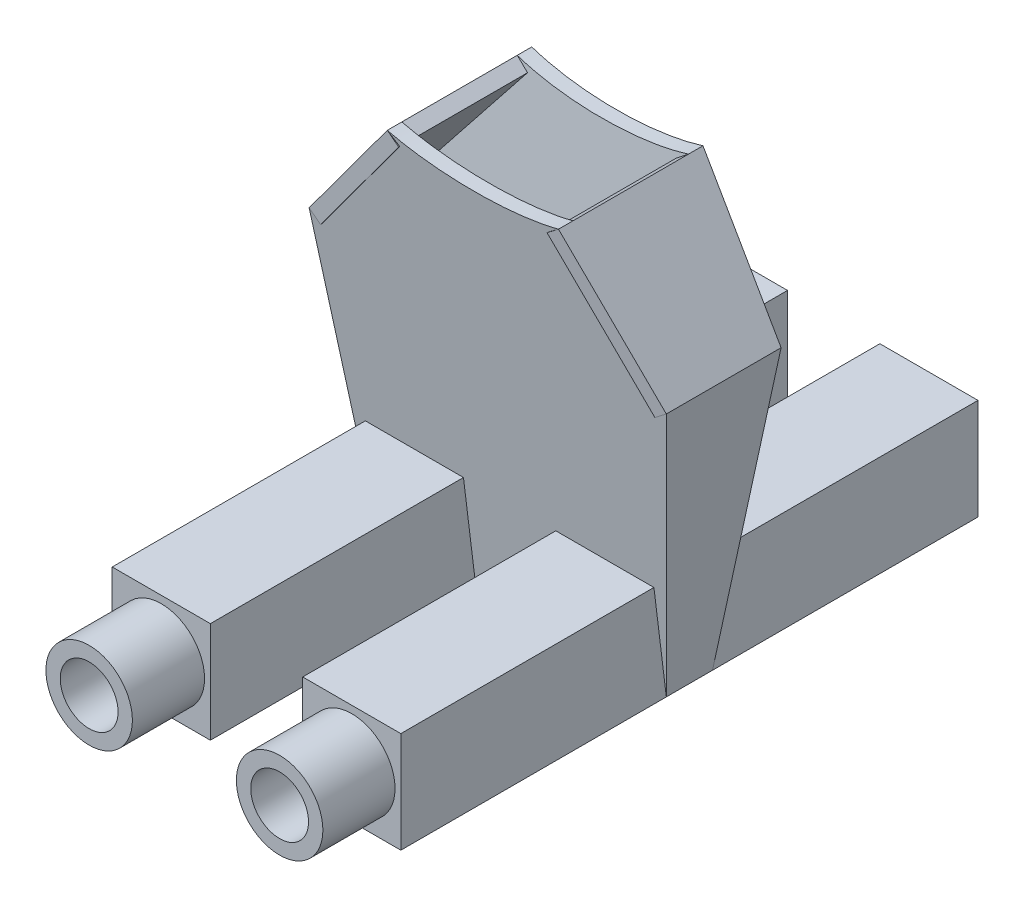
SolidWorks part; units mm, degrees
ref_plane "Front" through (0, 0, 0) normal (0, 0, 1) x (1, 0, 0)
ref_plane "Top" through (0, 0, 0) normal (0, 1, 0) x (1, 0, 0)
ref_plane "Right" through (0, 0, 0) normal (1, 0, 0) x (0, 0, -1)
sketch "Sketch1" plane through (0, 0, 0) normal (0, 1, 0) x (1, 0, 0)
  line L1 (-5, 0.8) -> (5, 0.8)
  line L2 (-5, 0.8) -> (-5, -0.8)
  line L3 (-5, -0.8) -> (5, -0.8)
  line L4 (5, 0.8) -> (5, -0.8)
  line L5 (-5, 0.8) -> (5, -0.8) construction
  line L6 (-5, -0.8) -> (5, 0.8) construction
  point P0 (0, 0)
  dimension "D1" = 1.6
  dimension "D2" = 10
extrude "Boss-Extrude1" add sketch "Sketch1" along normal blind 15 draft 7 draft outward yes
shell "Shell1" thickness 0.5 removed face at (0, 15, 0)
sketch "Sketch6" plane through (0, 0, 0) normal (0, -1, 0) x (1, 0, 0)
  line L1 (-1.6, -10) -> (-5, -10)
  line L2 (-1.6, -10) -> (-1.6, 10)
  line L3 (-1.6, 10) -> (-5, 10)
  line L4 (-5, -10) -> (-5, 10)
  line L5 (-1.6, -10) -> (-5, 10) construction
  line L6 (-1.6, 10) -> (-5, -10) construction
  line L7 (1.6, 10) -> (5, 10)
  line L8 (1.6, 10) -> (1.6, -10)
  line L9 (1.6, -10) -> (5, -10)
  line L10 (5, 10) -> (5, -10)
  line L11 (1.6, 10) -> (5, -10) construction
  line L12 (1.6, -10) -> (5, 10) construction
  point P0 (-3.3, 0)
  point P5 (3.3, 0)
  dimension "D1" = 3.4
  dimension "D2" = 20
  dimension "D3" = 3.4
extrude "Boss-Extrude2" add sketch "Sketch6" against normal blind 3.5 separate body
sketch "Sketch11" plane through (0, 0, 0) normal (0, 0, 1) x (1, 0, 0)
  line L1 (-6.8418, 15) -> (6.8418, 15) construction
  ellipse E0 centre (0, 15) end of major axis (4.5, 15) minor radius 1.5
extrude "Cut-Extrude11" cut sketch "Sketch11" against normal blind 10 and the other way blind 10
sketch "Sketch18" plane through (0, 0, 0) normal (0, 0, 1) x (1, 0, 0)
  line L0 (-2.9665, 13.8721) -> (-6.1886, 9.68)
  line L1 (-6.8418, 15) -> (-5, 0) construction
  line L2 (-6.1886, 9.68) -> (-6.9373, 15.7779)
  line L3 (-6.9373, 15.7779) -> (-2.9665, 15.7779)
  line L4 (-2.9665, 15.7779) -> (-2.9665, 13.8721)
extrude "Cut-Extrude12" cut sketch "Sketch18" against normal blind 10 and the other way blind 10
sketch "Sketch19" plane through (-8.5674, 6.5849, 0) normal (-0.7929, 0.6094, 0) x (0, 0, 1)
  line L0 (1.9886, 3.9037) -> (2.5033, 9.191)
  line L1 (2.5033, 9.191) -> (-2.5033, 9.191)
  line L2 (1.9886, 3.9037) -> (-1.9886, 3.9037)
  line L3 (-1.9886, 3.9037) -> (-2.5033, 9.191)
extrude "Boss-Extrude3" add sketch "Sketch19" against normal blind 0.5
mirror "Mirror2" about plane through (0, 0, 0) normal (1, 0, 0) of "Cut-Extrude12"
mirror "Mirror3" about plane through (0, 0, 0) normal (1, 0, 0) of "Boss-Extrude3"
sketch "Sketch20" plane through (0, 0, 10) normal (0, 0, 1) x (1, 0, 0)
  circle A0 centre (3.3, 1.75) radius 1.4991
  dimension "D1" = 2.9982
extrude "Boss-Extrude4" add sketch "Sketch20" along normal blind 2.5
sketch "Sketch22" plane through (0, 0, 12.5) normal (0, 0, 1) x (1, 0, 0)
  circle A0 centre (3.3, 1.75) radius 1.0014
  dimension "D1" = 2.0028
extrude "Cut-Extrude13" cut sketch "Sketch22" against normal blind 13
sketch "Sketch25" plane through (0, 3.5, 0) normal (0, 1, 0) x (1, 0, 0)
  line L1 (-4.372, 0.7261) -> (-2.372, 0.7261)
  line L2 (-4.372, 0.7261) -> (-4.372, -0.6739)
  line L3 (-4.372, -0.6739) -> (-2.372, -0.6739)
  line L4 (-2.372, 0.7261) -> (-2.372, -0.6739)
  line L5 (-4.372, 0.7261) -> (-2.372, -0.6739) construction
  line L6 (-4.372, -0.6739) -> (-2.372, 0.7261) construction
  point P0 (-3.372, 0.0261)
  dimension "D1" = 2
  dimension "D2" = 1.4
extrude "Cut-Extrude14" cut sketch "Sketch25" against normal blind 1.5
mirror "Mirror6" about plane through (0, 0, 0) normal (1, 0, 0) of "Cut-Extrude14"
sketch "Sketch28" plane through (0, 0, 10) normal (0, 0, 1) x (1, 0, 0)
  circle A0 centre (-3.3, 1.75) radius 1.4984
  dimension "D1" = 2.9967
extrude "Boss-Extrude5" add sketch "Sketch28" along normal blind 2.5
sketch "Sketch29" plane through (0, 0, 12.5) normal (0, 0, 1) x (1, 0, 0)
  circle A0 centre (-3.3, 1.75) radius 1.0022
  dimension "D1" = 2.0043
extrude "Cut-Extrude15" cut sketch "Sketch29" against normal blind 13
sketch "Sketch30" plane through (0, 0, 0) normal (0, -1, 0) x (1, 0, 0)
  line L0 (1.6, 10) -> (1.6, -10) construction
  line L1 (-1.6, 0.8) -> (1.6, 0.8)
  line L2 (-1.6, 0.8) -> (-1.6, -0.8)
  line L3 (-1.6, -0.8) -> (1.6, -0.8)
  line L4 (1.6, 0.8) -> (1.6, -0.8)
  line L5 (-1.6, 0.8) -> (1.6, -0.8) construction
  line L6 (-1.6, -0.8) -> (1.6, 0.8) construction
  line L7 (5, -0.8) -> (-5, -0.8) construction
  point P0 (0, 0)
extrude "Boss-Extrude6" add sketch "Sketch30" against normal blind 9 draft 6 draft outward yes
